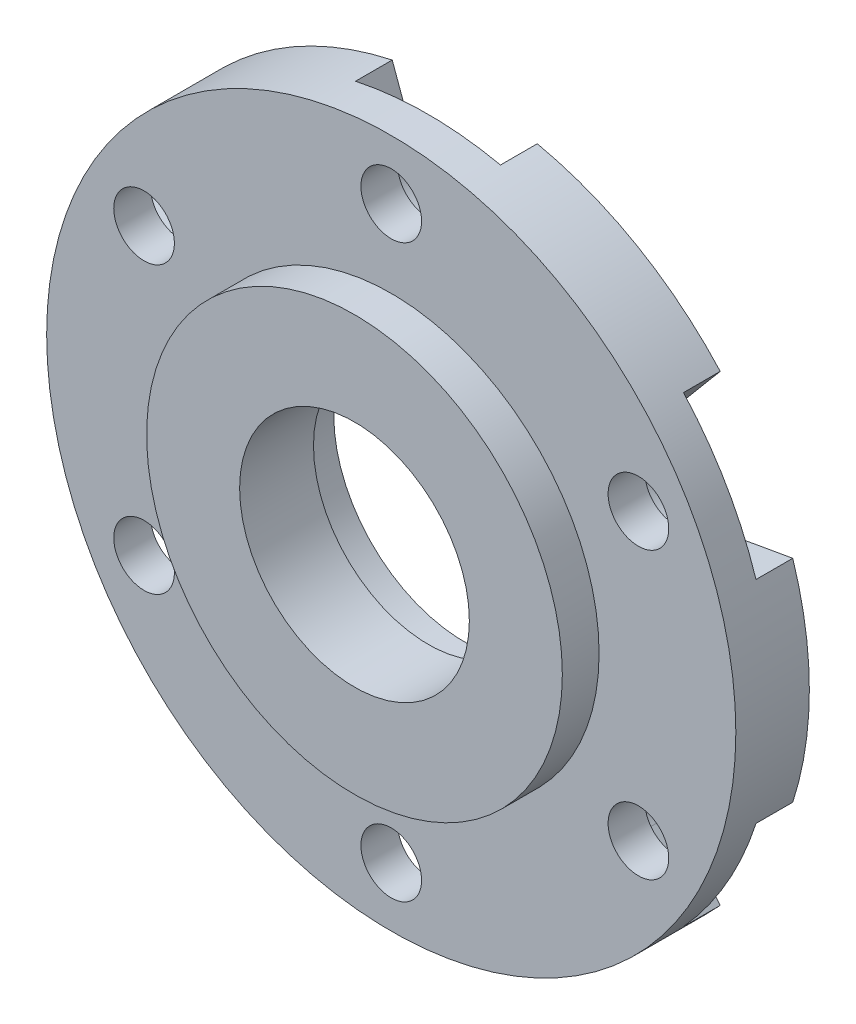
SolidWorks part; units mm, degrees
material "6061-T6 (SS)"
ref_plane "Front Plane" through (0, 0, 0) normal (0, 0, 1) x (1, 0, 0)
ref_plane "Top Plane" through (0, 0, 0) normal (0, 1, 0) x (1, 0, 0)
ref_plane "Right Plane" through (0, 0, 0) normal (1, 0, 0) x (0, 0, -1)
sketch "Sketch Spindle Skeleton" plane through (0, 0, 0) normal (1, 0, 0) x (0, 0, -1)
  line L0 (-108, -9.5) -> (-149, -9.5)
  line L5 (-1000, 0) -> (49000, 0)
  line L6 (0, -9.5) -> (0, 9.5)
  line L13 (0, 9.5) -> (-46.4, 9.5)
  line L26 (-46.4, 9.5) -> (-46.4, 14)
  line L27 (-46.4, 14) -> (-108, 14)
  line L32 (-108, 14) -> (-108, 9.5)
  line L34 (-165, 7) -> (-165, -7)
  line L36 (-108, -9.5) -> (-108, -14)
  line L37 (-108, -14) -> (-46.4, -14)
  line L38 (-46.4, -14) -> (-46.4, -9.5)
  line L39 (0, -9.5) -> (-46.4, -9.5)
  line L40 (-22.625, 37.5) -> (-14.625, 37.5)
  line L41 (-124.6, 22.6187) -> (-108, 22.6187)
  line L42 (-124.6, 22.6187) -> (-124.6, -22.6187)
  line L43 (-124.6, -22.6187) -> (-108, -22.6187)
  line L44 (-108, 22.6187) -> (-108, -22.6187)
  line L45 (-124.6, 22.6187) -> (-108, -22.6187) construction
  line L46 (-124.6, -22.6187) -> (-108, 22.6187) construction
  line L47 (-29.8, 22.6187) -> (-46.4, 22.6187)
  line L48 (-29.8, 22.6187) -> (-29.8, -22.6187)
  line L49 (-29.8, -22.6187) -> (-46.4, -22.6187)
  line L50 (-46.4, 22.6187) -> (-46.4, -22.6187)
  line L51 (-29.8, 22.6187) -> (-46.4, -22.6187) construction
  line L52 (-29.8, -22.6187) -> (-46.4, 22.6187) construction
  line L59 (-14.625, 37.5) -> (-14.625, -37.5)
  line L60 (-14.625, -37.5) -> (-22.625, -37.5)
  line L61 (-22.625, -22.6187) -> (-26.625, -22.6187)
  line L62 (-26.625, -22.6187) -> (-26.625, -12.5)
  line L63 (-26.625, -12.5) -> (-22.625, -12.5)
  line L64 (-22.625, -12.5) -> (-22.625, 12.5)
  line L65 (-22.625, 12.5) -> (-26.625, 12.5)
  line L66 (-26.625, 12.5) -> (-26.625, 22.6187)
  line L67 (-26.625, 22.6187) -> (-22.625, 22.6187)
  line L68 (-22.625, 22.6187) -> (-22.625, 37.5)
  line L69 (-22.625, -22.6187) -> (-22.625, -37.5)
  line L71 (-136.284, 37.5) -> (-23.625, 37.5)
  line L72 (-136.284, 37.5) -> (-136.284, -37.5)
  line L73 (-136.284, -37.5) -> (-23.625, -37.5)
  line L74 (-23.625, 37.5) -> (-23.625, -37.5)
  line L75 (-136.284, 37.5) -> (-23.625, -37.5) construction
  line L76 (-136.284, -37.5) -> (-23.625, 37.5) construction
  line L77 (-149, -9.5) -> (-149, -7)
  line L78 (-149, -7) -> (-165, -7)
  line L79 (-108, 9.5) -> (-149, 9.5)
  line L80 (-149, 7) -> (-165, 7)
  line L81 (-149, 9.5) -> (-149, 7)
  line L82 (-128.5, 9.5) -> (-128.5, -9.5) construction
  line L83 (-23.2, 9.5) -> (-23.2, -9.5) construction
  line L96 (-136.284, 37.5) -> (-144.284, 37.5)
  line L98 (-136.284, -37.5) -> (-144.284, -37.5)
  line L99 (-144.284, 37.5) -> (-144.284, -37.5)
  line L110 (-136.284, 37.5) -> (-136.284, -37.5)
  point P3 (0, 0)
  point P18 (-116.3, 0)
  point P24 (-38.1, 0)
  point P29 (-79.9545, 0)
  point P48 (-14.625, 31.0593)
  point P70 (-144.284, 31.0593)
revolve "Main Revolve" add sketch "Sketch Spindle Skeleton" angle 360 about L5 region at (0, 23.2432, 18.8195) region at (0, 17.5594, 25.125)
sketch "Sketch Center Cut" plane through (0, 0, 22.625) normal (0, 0, 1) x (1, 0, 0)
  circle A0 centre (0, 0) radius 12.5 construction
  circle A1 centre (0, 0) radius 12.5 construction
  circle A2 centre (0, 0) radius 12.5
  dimension "D1" = 25
extrude "Cut Center" cut sketch "Sketch Center Cut" against normal through all
hole_wizard "CBORE for M6 SHCS1" positions "Hole wizard sketch 1" profile "Hole wizard sketch 2" counterbore size "M6" standard "ANSI Metric" end condition through all
sketch "Hole wizard sketch 1" plane through (0, 0, 14.625) normal (0, 0, -1) x (-1, 0, 0)
  point P0 (0, 31.0593)
sketch "Hole wizard sketch 2" plane through (0, 31.0593, 14.625) normal (1, 0, 0) x (0, 1, 0)
  line L0 (0, 0) -> (0, 12)
  line L1 (0, 12) -> (3.3, 12)
  line L3 (3.3, 12) -> (3.3, 4)
  line L4 (3.3, 4) -> (5.5, 4)
  line L5 (5.5, 4) -> (5.5, 0)
  line L7 (5.5, 0) -> (0, 0)
  line L11 (0, -6.35) -> (0, 107.95) construction
  dimension "Thru Hole Dia." = 6.6
  dimension "Thru Hole Depth" = 12
  dimension "C'Bore Dia." = 11
  dimension "C'Bore Depth" = 4
pattern_circular "CirPattern1" count 6 over 360 about axis through (0, 0, 14.625) along (0, 0, 1) of "CBORE for M6 SHCS1"
sketch "Sketch1" plane through (0, 0, 14.625) normal (0, 0, -1) x (-1, 0, 0)
  circle A0 centre (0, 0) radius 14.2558
  dimension "D1" = 28.5115
extrude "Cut-Extrude1" cut sketch "Sketch1" against normal blind 3.9624
sketch "Sketch2" plane through (0, 0, 14.625) normal (0, 0, -1) x (-1, 0, 0)
  line L0 (-5.1683, 29.1782) -> (-7.8915, 36.6602)
  line L1 (0, 31.0593) -> (0, 37.5) construction
  line L2 (5.1683, 29.1782) -> (7.8915, 36.6602)
  line L3 (22.6849, 19.065) -> (27.8029, 25.1644)
  line L4 (27.8533, 10.1132) -> (35.6945, 11.4959)
  line L5 (27.8533, -10.1132) -> (35.6945, -11.4959)
  line L6 (22.6849, -19.065) -> (27.8029, -25.1644)
  line L7 (5.1683, -29.1782) -> (7.8915, -36.6602)
  line L8 (-5.1683, -29.1782) -> (-7.8915, -36.6602)
  line L9 (-22.6849, -19.065) -> (-27.8029, -25.1644)
  line L10 (-27.8533, -10.1132) -> (-35.6945, -11.4959)
  line L11 (-27.8533, 10.1132) -> (-35.6945, 11.4959)
  line L12 (-22.6849, 19.065) -> (-27.8029, 25.1644)
  circle A0 centre (0, 31.0593) radius 5.5 construction
  circle A1 centre (0, 0) radius 37.5 construction
  arc A2 (-5.1683, 29.1782) -> (5.1683, 29.1782) centre (0, 31.0593) ccw
  circle A3 centre (0, 0) radius 37.5
  arc A4 (22.6849, 19.065) -> (27.8533, 10.1132) centre (26.8982, 15.5297) ccw
  arc A5 (27.8533, -10.1132) -> (22.6849, -19.065) centre (26.8982, -15.5297) ccw
  arc A6 (5.1683, -29.1782) -> (-5.1683, -29.1782) centre (0, -31.0593) ccw
  arc A7 (-22.6849, -19.065) -> (-27.8533, -10.1132) centre (-26.8982, -15.5297) ccw
  arc A8 (-27.8533, 10.1132) -> (-22.6849, 19.065) centre (-26.8982, 15.5297) ccw
  point P37 (0, 0)
  circle M3 centre (-26.8982, 15.5297) radius 5.5
  circle M4 centre (-26.8982, -15.5297) radius 5.5
  circle M5 centre (0, -31.0593) radius 5.5
  circle M6 centre (26.8982, -15.5297) radius 5.5
  circle M7 centre (26.8982, 15.5297) radius 5.5
  circle M8 centre (0, 31.0593) radius 5.5
  circle M9 centre (0, 0) radius 37.5
  dimension "D1" = 20
  dimension "D2" = 6
extrude "Cut-Extrude2" cut sketch "Sketch2" against normal up to surface (4 mm away) contours M8 | L1 L2 M8 M9 | L1 A3 L0 M8 | L4 L3 M7 M9 | M7 | L6 L5 M6 M9 | M6 | M5 | L8 L7 M5 M9 | L10 L9 M4 M9 | M4 | L12 L11 M3 M9 | A3 M3 region at (4.3779, 34.1248, 14.625) region at (4.7535, 35.3844, 14.625) region at (-4.7535, 35.3844, 14.625) region at (25.3963, 21.9868, 14.625) region at (26.8982, 15.5297, 14.625) region at (-32.3037, 18.6505, 14.625) region at (31.7393, -11.0005, 14.625) region at (-26.8982, 15.5297, 14.625) region at (26.8982, -15.5297, 14.625) region at (6.3623, -32.9803, 14.625) region at (-32.3037, -18.6505, 14.625) region at (0, -31.0593, 14.625) region at (-26.8982, -15.5297, 14.625) up to face at (23.5982, -15.5297, 18.625)
